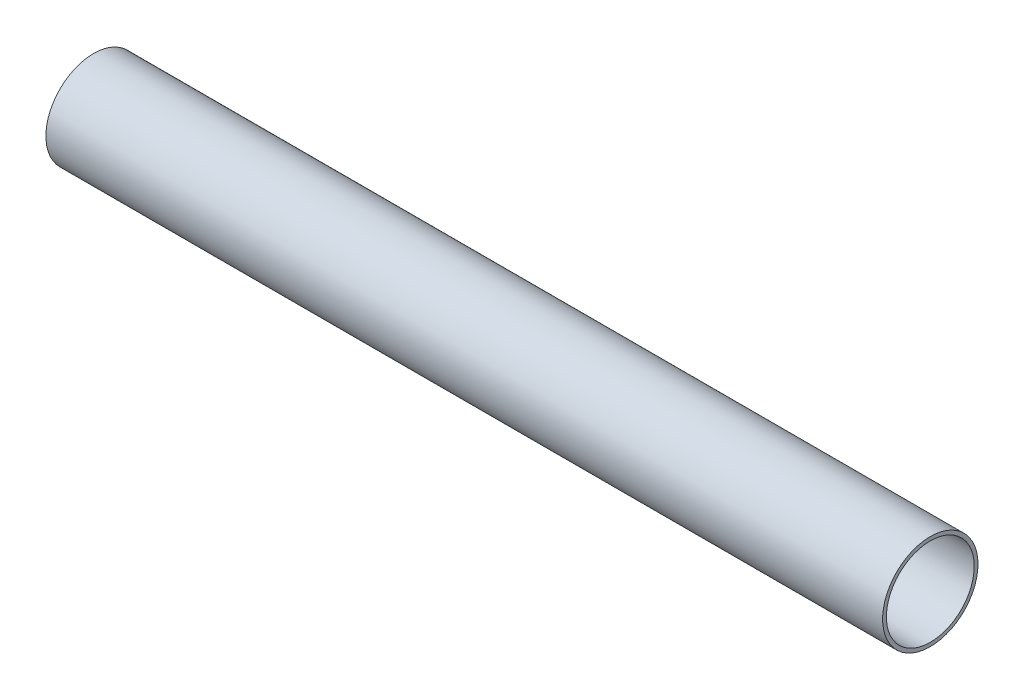
SolidWorks part; units mm, degrees
material "PVC 0.007 Plastificado"
ref_plane "Front" through (0, 0, 0) normal (0, 0, 1) x (1, 0, 0)
ref_plane "Top" through (0, 0, 0) normal (0, 1, 0) x (1, 0, 0)
ref_plane "Right" through (0, 0, 0) normal (1, 0, 0) x (0, 0, -1)
sketch "Croquis1" plane through (0, 0, 0) normal (1, 0, 0) x (0, 0, -1)
  circle A0 centre (0, 0) radius 57
  circle A1 centre (0, 0) radius 52.5
  dimension "D1" = 114
extrude "Saliente-Extruir1" add sketch "Croquis1" along normal blind 1000
